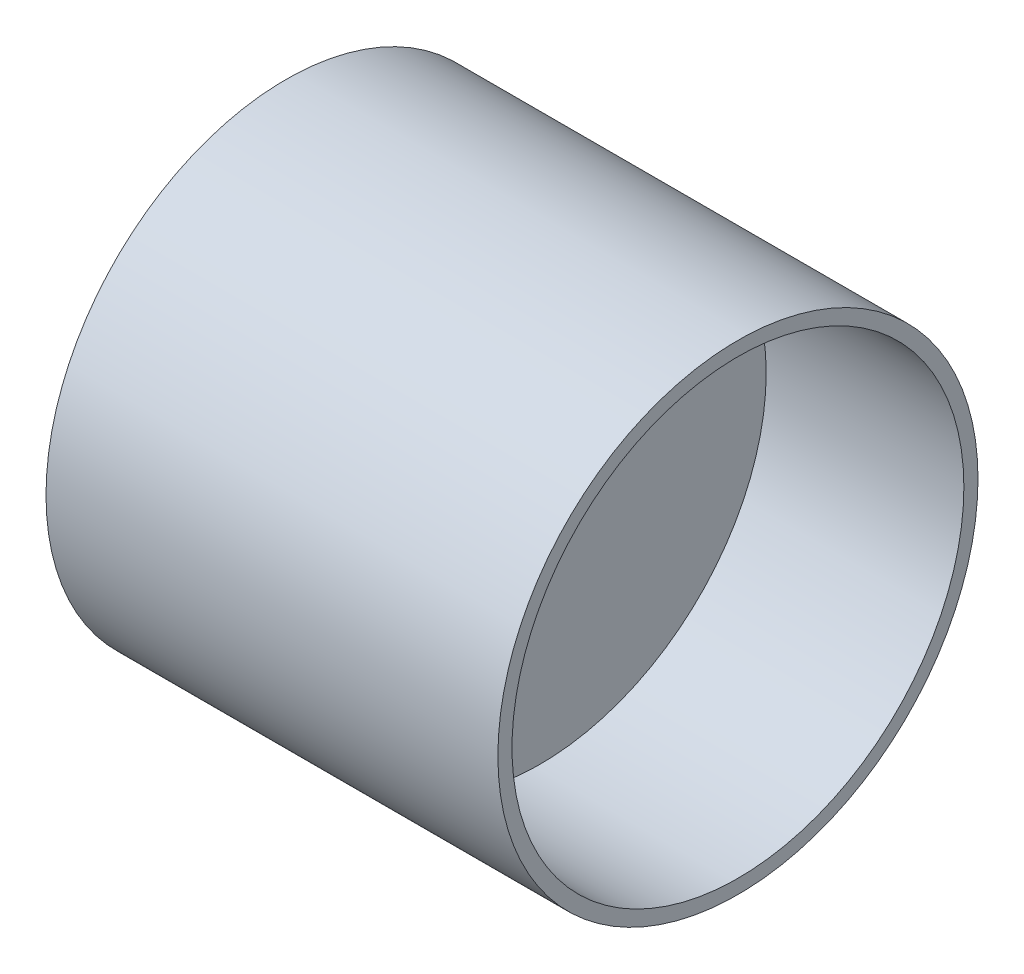
SolidWorks part; units mm, degrees
material "ABS"
ref_plane "Front Plane" through (0, 0, 0) normal (0, 0, 1) x (1, 0, 0)
ref_plane "Top Plane" through (0, 0, 0) normal (0, 1, 0) x (1, 0, 0)
ref_plane "Right Plane" through (0, 0, 0) normal (1, 0, 0) x (0, 0, -1)
sketch "Sketch1" plane through (0, 0, 0) normal (1, 0, 0) x (0, 0, -1)
  circle A0 centre (0, 0) radius 42.5
  dimension "D1" = 85
extrude "Boss-Extrude1" add sketch "Sketch1" along normal mid plane 100
ref_plane "Bolts" [suppressed] through (0, 40, 0) normal (0, 1, 0) x (1, 0, 0)
sketch "Sketch4" [suppressed] plane through (0, 40, 0) normal (0, 1, 0) x (1, 0, 0)
  line L0 (-50, 0) -> (50, 0) construction
  line L1 (50, -40) -> (50, 40) construction
  circle A0 centre (0, 0) radius 2
  circle A1 centre (30, 0) radius 2
  point P6 (0, 0)
  dimension "D3" = 4
  dimension "D1" = 30
  dimension "D2" = 50
extrude "Cut-Extrude2" [suppressed] cut sketch "Sketch4" against normal blind 15 contours A0
pattern_circular "CirPattern1" [suppressed] count 6 over 360 of bodies 103
sketch "Sketch6" plane through (50, 0, 0) normal (1, 0, 0) x (0, 0, -1)
  circle A0 centre (0, 0) radius 40
  circle A1 centre (0, 0) radius 42.5 construction
  dimension "D1" = 2.5
extrude "Cut-Extrude6" cut sketch "Sketch6" against normal blind 35
ref_plane "Plane1" through (0, 42.5, 0) normal (0, 1, 0) x (1, 0, 0)
sketch "Sketch9" plane through (-50, 0, 0) normal (-1, 0, 0) x (0, 0, 1)
  circle A1 centre (0, 0) radius 42.5
  circle A3 centre (0, 0) radius 42.5
  dimension "D1" = 0
extrude "Cut-Extrude12" cut sketch "Sketch9" against normal blind 20
